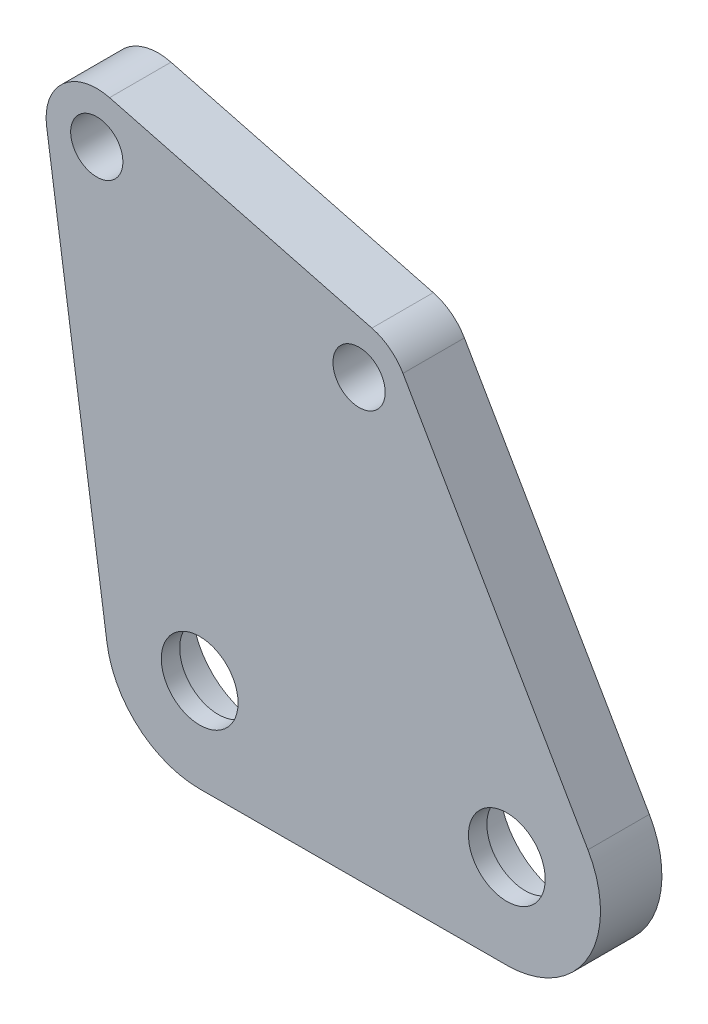
SolidWorks part; units mm, degrees
ref_plane "Front Plane" through (0, 0, 0) normal (0, 0, 1) x (1, 0, 0)
ref_plane "Top Plane" through (0, 0, 0) normal (0, 1, 0) x (1, 0, 0)
ref_plane "Right Plane" through (0, 0, 0) normal (1, 0, 0) x (0, 0, -1)
sketch "Sketch1" plane through (0, 0, 0) normal (0, 0, 1) x (1, 0, 0)
  line L0 (19.9767, -24.7037) -> (86.7267, -91.4537) construction
  line L5 (11.7267, -24.7037) -> (15.7267, -24.7037) construction
  line L6 (21.5029, 59.0001) -> (121.5029, 59.0001) construction
  line L7 (123.7267, 61.6601) -> (123.7267, -138.3399) construction
  line L8 (8.7267, 61.6601) -> (130.7267, 61.6601) construction
  line L9 (8.7267, 61.6601) -> (8.7267, -138.3399) construction
  line L10 (8.7267, -138.3399) -> (130.7267, -138.3399) construction
  line L11 (130.7267, 61.6601) -> (130.7267, -138.3399) construction
  line L12 (21.5029, 59.0001) -> (21.5029, -40.9999) construction
  line L13 (21.5029, -40.9999) -> (121.5029, -40.9999) construction
  line L14 (121.5029, 59.0001) -> (121.5029, -40.9999) construction
  line L15 (21.4768, -91.5934) -> (25.4768, -91.5934) construction
  line L16 (54.426, -35.8435) -> (58.426, -35.8435) construction
  line L17 (101.9767, -91.4537) -> (97.9767, -91.4537) construction
  line L18 (22.0593, -16.7209) -> (64.7586, -27.8607)
  line L19 (69.8191, -31.7157) -> (99.9306, -83.8235)
  line L20 (86.7693, -106.7036) -> (36.7695, -106.8434)
  line L21 (21.634, -93.777) -> (11.8117, -25.8849)
  circle A6 centre (27.9031, -215.7989) radius 11.25 construction
  circle A7 centre (27.9031, -215.7989) radius 6.25 construction
  circle A9 centre (86.7267, -91.4537) radius 11.25
  circle A10 centre (86.7267, -91.4537) radius 6.25
  circle A11 centre (19.9767, -24.7037) radius 11.25 construction
  circle A12 centre (19.9767, -24.7037) radius 6.25 construction
  circle A13 centre (36.7268, -91.5934) radius 11.25
  circle A14 centre (36.7268, -91.5934) radius 6.25
  circle A15 centre (-189.8804, -11.7635) radius 11.25
  circle A16 centre (-189.8804, -11.7635) radius 6.25
  circle A17 centre (86.7267, -91.4537) radius 44 construction
  circle A18 centre (86.7267, -91.4537) radius 40 construction
  circle A19 centre (36.7268, -91.5934) radius 10 construction
  circle A20 centre (36.7268, -91.5934) radius 18.5 construction
  circle A21 centre (19.9767, -24.7037) radius 4.25
  circle A22 centre (62.676, -35.8435) radius 4.25
  circle A23 centre (36.7268, -91.5934) radius 15.25
  circle A24 centre (86.7267, -91.4537) radius 15.25
  circle A25 centre (62.676, -35.8435) radius 8.25
  circle A26 centre (19.9767, -24.7037) radius 8.25
  point P52 (0, 0)
  dimension "D1" = 122
  dimension "D2" = 4
  dimension "D3" = 80
  dimension "D4" = 200
  dimension "D7" = 20
  dimension "D8" = 37
  dimension "D11" = 4
  dimension "D5" = 115
  dimension "D6" = 45
  dimension "D9" = 100
  dimension "D10" = 100
  dimension "BearingMajorDiameter" = 22.5
  dimension "BearingMinorDiameter" = 12.5
  dimension "AxleMajorDiameter" = 8.5
extrude "Boss-Extrude2" add sketch "Sketch1" along normal blind 10 contours A26 L21 A23 L20 A24 L19 A25 L18 | A25 A22 | A23 A13 | A24 A9 | A26 A21 | A13 A14 | A9 A10
extrude "Cut-Extrude5" cut sketch "Sketch1<5>" along normal blind 7 contours A13 | A9
sketch "Sketch1<5>" plane through (0, 0, 0) normal (0, 0, 1) x (1, 0, 0) same geometry as "Sketch1"
equation "\"BearingMajorDiameter\"= 22 + 0.5"
equation "\"BearingMinorDiameter\"= 12 + 0.5"
equation "\"AxleMajorDiameter\"= 8 + 0.5"
